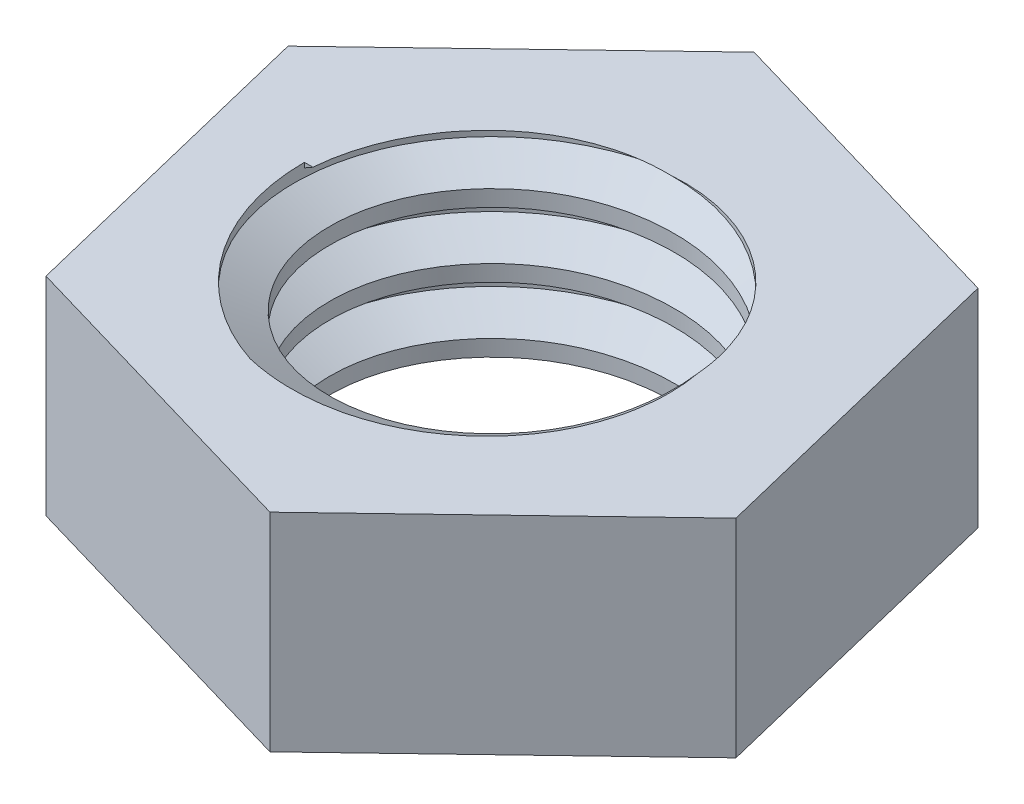
SolidWorks part; units mm, degrees
ref_plane "Front Plane" through (0, 0, 0) normal (0, 0, 1) x (1, 0, 0)
ref_plane "Top Plane" through (0, 0, 0) normal (0, 1, 0) x (1, 0, 0)
ref_plane "Right Plane" through (0, 0, 0) normal (1, 0, 0) x (0, 0, -1)
sketch "Sketch1" plane through (0, 0, 0) normal (0, 1, 0) x (1, 0, 0)
  line L1 (4.5903, 4.3889) -> (-1.5058, 6.1698)
  line L2 (-1.5058, 6.1698) -> (-6.0961, 1.7808)
  line L3 (-6.0961, 1.7808) -> (-4.5903, -4.3889)
  line L4 (-4.5903, -4.3889) -> (1.5058, -6.1698)
  line L5 (1.5058, -6.1698) -> (6.0961, -1.7808)
  line L6 (6.0961, -1.7808) -> (4.5903, 4.3889)
  circle A1 centre (0, 0) radius 5.5 construction
  dimension "D1" = 11
extrude "Boss-Extrude1" add sketch "Sketch1" along normal blind 4
sketch "Sketch2" plane through (0, 4, 0) normal (0, 1, 0) x (1, 0, 0)
  circle A0 centre (0, 0) radius 4
extrude "Cut-Extrude1" cut sketch "Sketch2" against normal through all
thread "Thread2" pitch 1.25 start angle 0, offset 1, length 8, pitch 1.25, diameter 8
ref_plane "Plane2" through (-4, 5, 0) normal (0, 0, 1) x (-1, 0, 0)
sketch "Thread Profile2" plane through (-4, 5, 0) normal (0, 0, 1) x (-1, 0, 0)
  line L0 (0, 0) -> (0, 1.25) construction
  line L11 (0, 0) -> (0, 1.0937)
  line L12 (0, 1.0937) -> (-0.6766, 0.7031)
  line L13 (-0.6766, 0.7031) -> (-0.6766, 0.3906)
  line L15 (-0.6766, 0.3906) -> (0, 0)
  line L17 (-0.6766, 0.5469) -> (0, 0.5469) construction
  point P2 (0, 0)
  dimension "Pitch" = 1.25
  dimension "Profile_Angle" = 60
  dimension "Profile_Land" = 0.3125
  dimension "Profile_Height" = 0.6766
sketch "Sketch7" plane through (0, 0, 0) normal (0, -1, 0) x (1, 0, 0)
  circle A0 centre (-8.7275, 7.0288) radius 21.0283
extrude "Cut-Extrude2" cut sketch "Sketch7" along normal through all
sketch "Sketch8" plane through (0, 4, 0) normal (0, 1, 0) x (1, 0, 0)
  circle A0 centre (-10.1137, 5.9354) radius 21.0374
extrude "Cut-Extrude3" cut sketch "Sketch8" along normal through all
